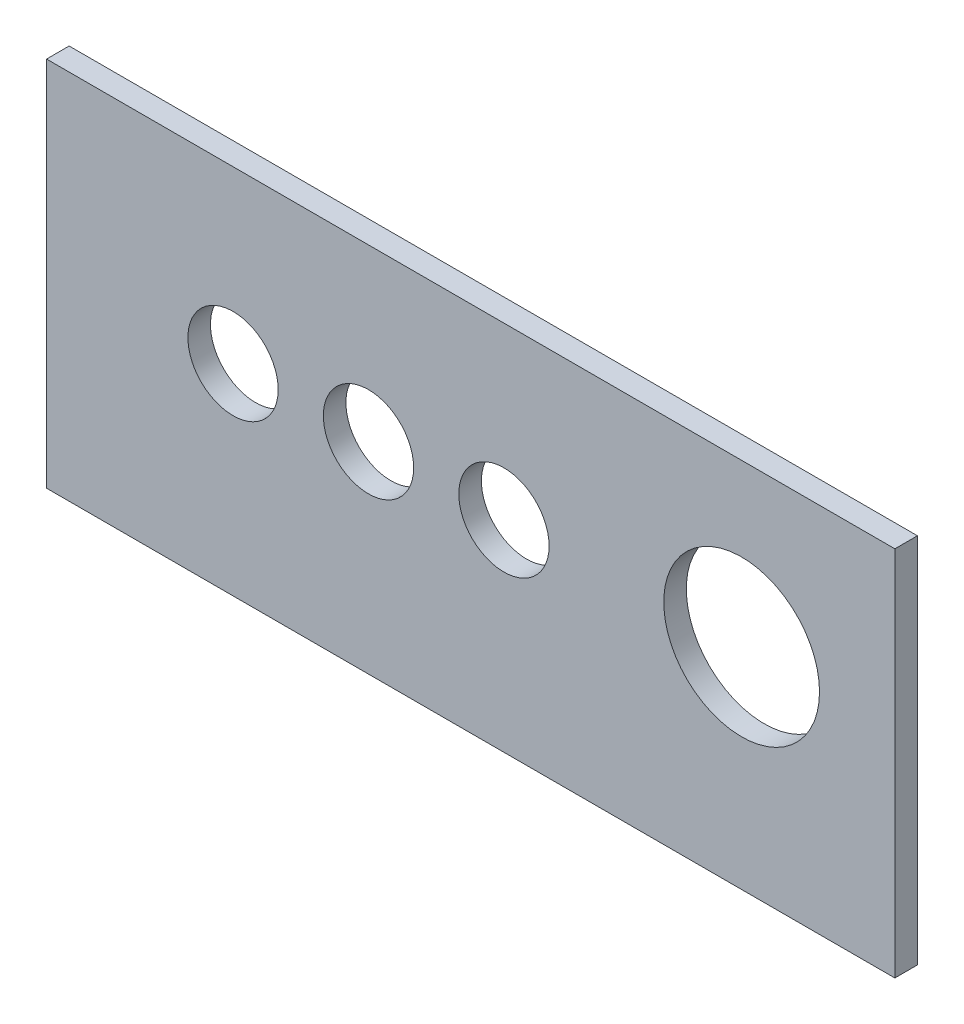
SolidWorks part; units mm, degrees
ref_plane "Front Plane" through (0, 0, 0) normal (0, 0, 1) x (1, 0, 0)
ref_plane "Top Plane" through (0, 0, 0) normal (0, 1, 0) x (1, 0, 0)
ref_plane "Right Plane" through (0, 0, 0) normal (1, 0, 0) x (0, 0, -1)
ref_axis "Axis1" through (0, -55, 0) along (0, 1, 0)
sketch "Model" plane through (0, 0, 0) normal (0, 0, 1) x (1, 0, 0)
  line L0 (484.3986, 216.9969) -> (484.3986, 7.9019)
  line L2 (7.2093, 7.9019) -> (7.2093, 216.9969)
  line L3 (7.2093, 7.9019) -> (484.3986, 7.9019)
  line L6 (7.2093, 216.9969) -> (484.3986, 216.9969)
  arc A0 (239.0985, 121.0969) -> (289.8985, 121.0969) centre (264.4985, 121.0969) ccw
  arc A1 (289.8985, 121.0969) -> (239.0985, 121.0969) centre (264.4985, 121.0969) ccw
  arc A2 (162.8985, 121.0969) -> (213.6985, 121.0969) centre (188.2985, 121.0969) ccw
  arc A3 (213.6985, 121.0969) -> (162.8985, 121.0969) centre (188.2985, 121.0969) ccw
  arc A42 (137.4985, 121.0969) -> (86.6985, 121.0969) centre (112.0985, 121.0969) ccw
  arc A43 (86.6985, 121.0969) -> (137.4985, 121.0969) centre (112.0985, 121.0969) ccw
  arc A44 (442.019, 126.1034) -> (354.389, 126.1034) centre (398.204, 126.1034) ccw
  arc A45 (354.389, 126.1034) -> (442.019, 126.1034) centre (398.204, 126.1034) ccw
extrude "Boss-Extrude1" add sketch "Model" along normal blind 12.7
sketch "Sketch2" plane through (0, 0, 12.7) normal (0, 0, 1) x (1, 0, 0)
  line L0 (7.2093, 216.9969) -> (484.3986, 7.9019) construction
  line L1 (484.3986, 7.9019) -> (484.3986, 216.9969) construction
  line L2 (484.3986, 216.9969) -> (7.2093, 7.9019) construction
  point P4 (248.4416, 111.2936)
ref_plane "Plane1" through (245.804, 0, 0) normal (1, 0, 0) x (0, 0, -1)
